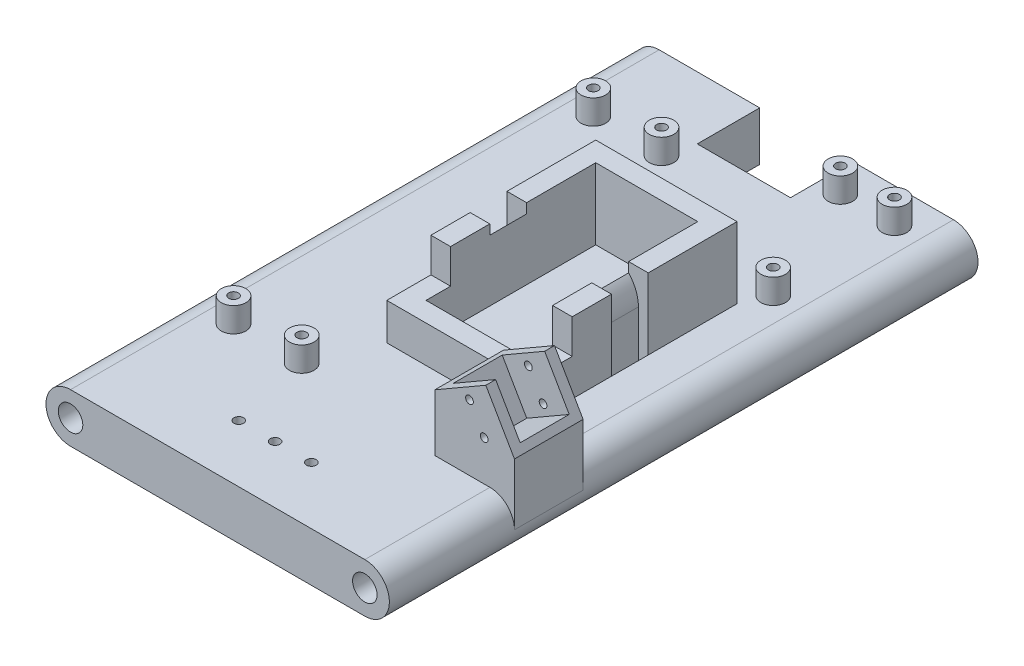
SolidWorks part; units mm, degrees
note: '?' marks a value the reader was unsure of. The reader was unsure of these and kept them because the rebuilt part matched: shared geometry of "Sketch6<2>".
ref_plane "Front Plane" through (0, 0, 0) normal (0, 0, 1) x (1, 0, 0)
ref_plane "Top Plane" through (0, 0, 0) normal (0, 1, 0) x (1, 0, 0)
ref_plane "Right Plane" through (0, 0, 0) normal (1, 0, 0) x (0, 0, -1)
sketch "Sketch2" plane through (0, 0, 0) normal (0, 0, 1) x (1, 0, 0)
  line L0 (-38.1, 6.35) -> (38.1, 6.35)
  line L1 (-38.1, -6.35) -> (38.1, -6.35)
  arc A0 (-38.1, -6.35) -> (-38.1, 6.35) centre (-38.1, 0) cw
  arc A1 (38.1, -6.35) -> (38.1, 6.35) centre (38.1, 0) ccw
  point P16 (0, 6.35)
  dimension "D3" = 6.35
  dimension "D2" = 76.2
extrude "Boss-Extrude1" add sketch "Sketch2" along normal blind 152.4 contours L0 A1 L1 A0
sketch "Sketch3" plane through (0, 0, 0) normal (0, 0, -1) x (-1, 0, 0)
  circle A0 centre (-38.1, 0) radius 3.175
  circle A1 centre (38.1, 0) radius 3.175
  dimension "D1" = 6.35
extrude "Cut-Extrude1" cut sketch "Sketch3" against normal through all
ref_axis "Axis1" through (0, 0, 0) along (0, 0, -1)?
sketch "Sketch5" plane through (0, 0, 152.4) normal (0, 0, 1) x (1, 0, 0)
  line L0 (26.0404, 22.3668) -> (32.3904, 11.3683)
  line L1 (32.3904, 11.3683) -> (43.3889, 17.7183)
  line L2 (43.3889, 17.7183) -> (44.45, 15.8804)
  line L4 (44.45, 15.8804) -> (44.45, 0)
  line L5 (32.6104, 11.4953) -> (43.169, 17.5913) construction
  line L6 (26.1674, 22.1468) -> (32.2634, 11.5882) construction
  line L7 (26.0404, 22.3668) -> (23.8407, 21.0968)
  line L8 (23.8407, 21.0968) -> (23.8407, 6.35)
  line L9 (-38.1, 6.35) -> (38.1, 6.35) construction
  line L10 (23.8407, 6.35) -> (38.1, 6.35)
  line L11 (36.819, 28.5898) -> (26.2604, 22.4938) construction
  line L12 (37.1659, 28.4968) -> (43.2619, 17.9382) construction
  arc A0 (38.1, -6.35) -> (38.1, 6.35) centre (38.1, 0) ccw construction
  arc A1 (38.1, 6.35) -> (44.45, 0) centre (38.1, 0) cw
  dimension "D2" = 2.54
extrude "Boss-Extrude2" add sketch "Sketch5" against normal up to vertex (47.625 mm away) from vertex at -34.925 contours L2 L4 A1 L10 L8 L7 L0 L1
sketch "Sketch6" plane through (0, 0, 117.475) normal (0, 0, 1) x (1, 0, 0)
  line L0 (23.8407, 6.35) -> (38.1, 6.35)
  line L1 (44.45, 15.8804) -> (44.45, 0) construction
  line L2 (44.45, 0) -> (44.45, 15.8804)
  line L3 (44.45, 15.8804) -> (37.0389, 28.7168)
  line L4 (37.0389, 28.7168) -> (23.8407, 21.0968)
  line L5 (23.8407, 21.0968) -> (23.8407, 6.35)
  arc A0 (38.1, 6.35) -> (44.45, 0) centre (38.1, 0) cw
  arc A1 (38.1, -6.35) -> (38.1, 6.35) centre (38.1, 0) ccw construction
extrude "Boss-Extrude3" add sketch "Sketch6" along normal blind 2.54
extrude "Boss-Extrude4" add sketch "Sketch6<2>" against normal blind 2.54 from surface at -12.7 starting at face at (34.727, 12.8057, 104.775)
sketch "Sketch6<2>" plane through (0, 0, 117.475) normal (0, 0, 1) x (1, 0, 0) same geometry as "Sketch6"
extrude "Cut-Extrude2" cut sketch "Sketch7" against normal blind 25.4
sketch "Sketch7" plane through (-48.529, -83.6237, 120.015) normal (0, 0, 1) x (1, 0, 0)
  circle A0 centre (85.1487, 100.3666) radius 1
  circle A1 centre (81.3387, 106.9658) radius 1
sketch "Sketch8" plane through (0, 6.35, 0) normal (0, 1, 0) x (1, 0, 0)
  line L1 (-7.6553, -46.863) -> (28.9207, -46.863)
  line L2 (-7.6553, -46.863) -> (-7.6553, -100.965)
  line L3 (-7.6553, -100.965) -> (28.9207, -100.965)
  line L4 (28.9207, -46.863) -> (28.9207, -100.965)
  line L5 (9.0452, -51.943) -> (-0.9878, -51.943) construction
  line L6 (-2.5753, -51.943) -> (23.8407, -51.943)
  line L7 (-2.5753, -51.943) -> (-2.5753, -95.885)
  line L8 (-2.5753, -95.885) -> (23.8407, -95.885)
  line L9 (23.8407, -51.943) -> (23.8407, -95.885)
  line L10 (-2.5753, -94.2975) -> (-2.5753, -53.5305) construction
  line L11 (23.8407, -53.5305) -> (23.8407, -94.2975) construction
  line L12 (22.2532, -95.885) -> (12.2202, -95.885) construction
  line L13 (-2.5753, -51.943) -> (-7.6553, -51.943) construction
  line L14 (-7.6553, -51.943) -> (-2.5753, -51.943) construction
  line L15 (-2.5753, -51.943) -> (-2.5753, -46.863) construction
  line L17 (23.8407, -95.885) -> (23.8407, -100.965) construction
  line L18 (23.8407, -95.885) -> (28.9207, -95.885) construction
  dimension "D1" = 5.08
extrude "Boss-Extrude5" add sketch "Sketch8" along normal offset from surface (18.415 mm away) 2.54
extrude "Cut-Extrude3" cut sketch "Sketch9" against normal blind 50.8
sketch "Sketch9" plane through (28.9207, -83.6237, -42.4096) normal (1, 0, 0) x (0, 0, -1)
  line L1 (-143.3746, 108.3887) -> (-131.9446, 108.3887)
  line L2 (-143.3746, 108.3887) -> (-143.3746, 99.4987)
  line L3 (-143.3746, 99.4987) -> (-131.9446, 99.4987)
  line L4 (-131.9446, 108.3887) -> (-131.9446, 99.4987)
sketch "Sketch11" plane through (0, 6.35, 0) normal (0, 1, 0) x (1, 0, 0)
  circle A0 centre (31.765, -8.938) radius 1.65 construction
  point P0 (31.765, -8.938)
  point P3 (31.765, -40.338)
  point P4 (17.765, -40.338)
  point P6 (17.765, -8.938)
  point P8 (-14.075, -23.415)
  point P10 (-31.725, -23.415)
  point P12 (-31.725, -116.565)
  point P14 (-14.075, -116.565)
sketch "Sketch10" plane through (0, 6.35, 0) normal (0, 1, 0) x (1, 0, 0)
  circle A0 centre (31.765, -8.938) radius 3.175
  circle A1 centre (31.765, -8.938) radius 1.25
  dimension "D1" = 6.35
  dimension "D2" = 2.5
extrude "Boss-Extrude6" add sketch "Sketch10" along normal up to surface (6.35 mm away)
sketch "Sketch12" plane through (0, 6.35, 0) normal (0, 1, 0) x (1, 0, 0)
  circle A0 centre (31.765, -8.938) radius 1.25
  circle A1 centre (31.765, -8.938) radius 1.25 construction
extrude "Cut-Extrude4" cut sketch "Sketch12" against normal through all
pattern_sketch "Sketch-Pattern1" of "Boss-Extrude6", "Cut-Extrude4" driven by "Sketch11"
extrude "Cut-Extrude5" cut sketch "Sketch13" against normal through all
sketch "Sketch13" plane through (55.0397, 6.35, 304.7582) normal (0, 1, 0) x (-1, 0, 0)
  line L1 (42.9747, -304.7582) -> (67.1047, -304.7582)
  line L2 (42.9747, -304.7582) -> (42.9747, -288.5921)
  line L3 (42.9747, -288.5921) -> (67.1047, -288.5921)
  line L4 (67.1047, -304.7582) -> (67.1047, -288.5921)
extrude "Cut-Extrude6" cut sketch "Sketch14" against normal blind 9.525 from offset 69.85 offset against normal yes
sketch "Sketch14" plane through (-48.529, -83.6237, 0) normal (0, 0, -1) x (-1, 0, 0)
  line L1 (-74.9097, 99.4987) -> (-74.9097, 77.2737)
  line L2 (-74.9097, 77.2737) -> (-77.4497, 77.2737)
  line L3 (-77.4497, 77.2737) -> (-77.4497, 108.3887)
  line L4 (-77.4497, 108.3887) -> (-72.3697, 108.3887)
  line L5 (-72.3697, 108.3887) -> (-72.3697, 105.8487)
  line L7 (-45.9537, 105.8487) -> (-45.9537, 108.3887)
  line L9 (-45.9537, 108.3887) -> (-40.8737, 108.3887)
  line L10 (-40.8737, 108.3887) -> (-40.8737, 77.2737)
  line L11 (-40.8737, 77.2737) -> (-43.4137, 77.2737)
  line L12 (-43.4137, 77.2737) -> (-43.4137, 99.4987)
  arc A0 (-74.9097, 99.4987) -> (-72.3697, 105.8487) centre (-65.7022, 99.4987) cw
  arc A1 (-43.4137, 99.4987) -> (-45.9537, 105.8487) centre (-52.6212, 99.4987) ccw
extrude "Cut-Extrude7" cut sketch "Sketch15" against normal through all
sketch "Sketch15" plane through (-48.529, 6.35, -42.4096) normal (0, 1, 0) x (1, 0, 0)
  circle A1 centre (57.927, -179.9506) radius 1.25
  circle A2 centre (48.529, -179.9506) radius 1.25
  circle A3 centre (39.131, -179.9506) radius 1.25
